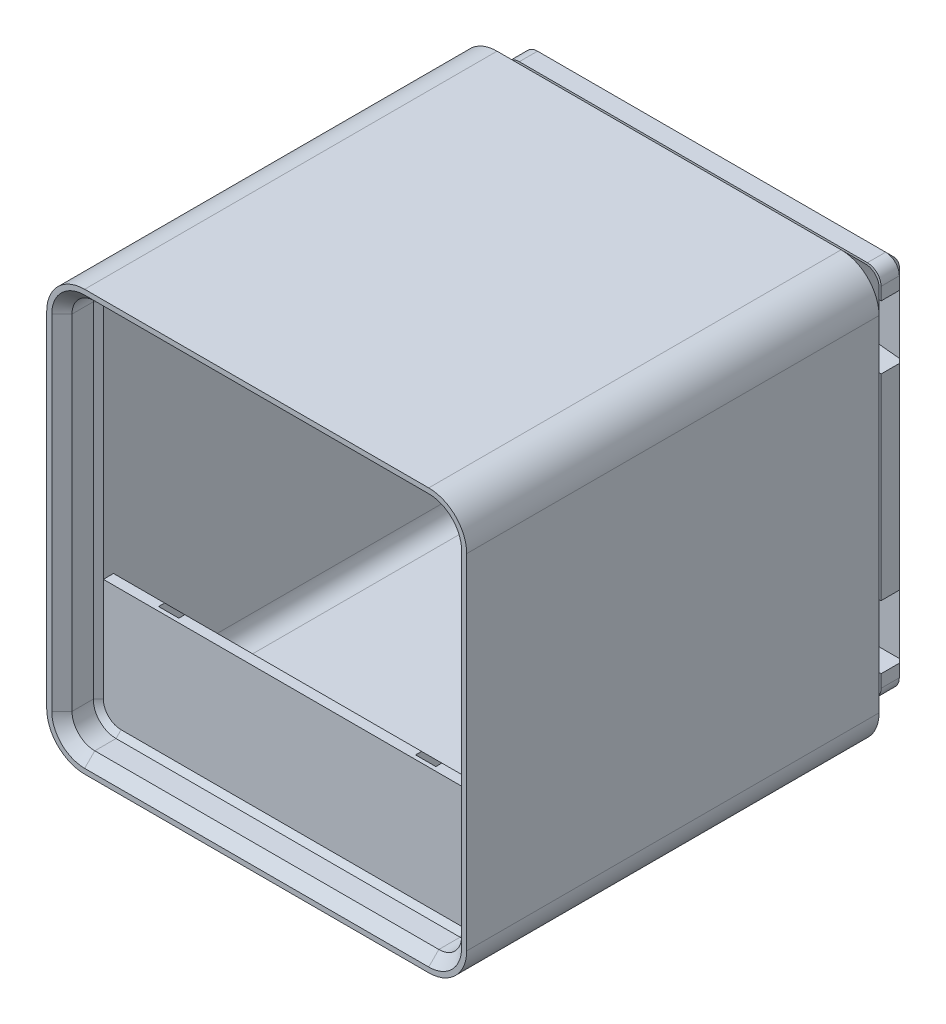
SolidWorks part; units mm, degrees
ref_plane "Front Plane" through (0, 0, 0) normal (0, 0, 1) x (1, 0, 0)
ref_plane "Top Plane" through (0, 0, 0) normal (0, 1, 0) x (1, 0, 0)
ref_plane "Right Plane" through (0, 0, 0) normal (1, 0, 0) x (0, 0, -1)
sketch "Sketch1" plane through (0, 0, 0) normal (0, 0, 1) x (1, 0, 0)
  line L1 (18.55, 18.55) -> (-18.55, 18.55)
  line L2 (18.55, 18.55) -> (18.55, -18.55)
  line L3 (18.55, -18.55) -> (-18.55, -18.55)
  line L4 (-18.55, 18.55) -> (-18.55, -18.55)
  line L5 (18.55, 18.55) -> (-18.55, -18.55) construction
  line L6 (18.55, -18.55) -> (-18.55, 18.55) construction
  point P0 (0, 0)
  dimension "D1" = 37.1
extrude "Boss-Extrude1" add sketch "Sketch1" along normal blind 2.6
sketch "Sketch2" plane through (0, 0, 2.6) normal (0, 0, 1) x (1, 0, 0)
  line L1 (-20.75, 20.75) -> (20.75, 20.75)
  line L2 (-20.75, 20.75) -> (-20.75, -20.75)
  line L3 (-20.75, -20.75) -> (20.75, -20.75)
  line L4 (20.75, 20.75) -> (20.75, -20.75)
  line L5 (-20.75, 20.75) -> (20.75, -20.75) construction
  line L6 (-20.75, -20.75) -> (20.75, 20.75) construction
  point P0 (0, 0)
  dimension "D1" = 41.5
extrude "Boss-Extrude2" add sketch "Sketch2" along normal blind 2.4
sketch "Sketch8" plane through (0, 0, 2.6) normal (0, 0, -1) x (-1, 0, 0)
  line L0 (-18.55, 18.55) -> (-18.55, 5.0094) construction
  line L1 (-18.55, -18.55) -> (-18.55, 18.55) construction
  line L2 (-14.65, 10.1) -> (-18.55, 9.7)
  line L11 (-12.7, 15.95) -> (-18.55, 15.95)
  line L12 (-12.7, 12.7) -> (-12.7, -12.7)
  line L13 (-12.7, -12.7) -> (12.7, -12.7)
  line L14 (12.7, -12.7) -> (12.7, 12.7)
  line L15 (12.7, 12.7) -> (-12.7, 12.7)
  line L16 (-12.7, 9.45) -> (-12.7, -12.7) construction
  line L22 (-18.55, 15.95) -> (-18.55, 9.7)
  arc A0 (-12.7, 15.95) -> (-12.7, 9.45) centre (-12.7, 12.7) cw
  arc A1 (-12.7, 9.45) -> (-14.65, 10.1) centre (-12.7, 12.7) cw
  dimension "D4" = 5.85
  dimension "D5" = 6.25
  dimension "D2" = 6.5
  dimension "D1" = 8.05
extrude "Base Magnet Slot" cut sketch "Sketch8" against normal blind 0.4 and the other way blind 2.2
sketch "Sketch12" plane through (0, 0, 0) normal (0, 0, -1) x (-1, 0, 0)
  line L0 (-12.7, 12.7) -> (-6.2, 12.7) construction
  line L1 (-12.7, 13.7) -> (-6.2, 13.7)
  line L2 (-12.7, 11.7) -> (-6.2, 11.7)
  arc A8 (-14.65, 10.1) -> (-12.7, 15.95) centre (-12.7, 12.7) ccw construction
  arc A9 (-14.65, 10.1) -> (-12.7, 15.95) centre (-12.7, 12.7) ccw construction
  arc A10 (-12.7, 13.7) -> (-12.7, 11.7) centre (-12.7, 12.7) ccw
  arc A11 (-6.2, 11.7) -> (-6.2, 13.7) centre (-6.2, 12.7) ccw
  point P3 (-9.45, 12.7)
  dimension "D1" = 2
  dimension "D2" = 6.5
extrude "Cut-Extrude1" cut sketch "Sketch12" against normal up to surface (2.6 mm away) up to face at (0, 0, 2.6)
mirror "Mirror1" about plane through (0, 0, 0) normal (0, 1, 0) of "Cut-Extrude1", "Base Magnet Slot"
mirror "Mirror2" about plane through (0, 0, 0) normal (1, 0, 0) of "Mirror1"
fillet "Fillet1" radius 1.35 4 edges at (18.55, 18.55, 1.3) (18.55, -18.55, 1.3) (-18.55, -18.55, 1.3) (-18.55, 18.55, 1.3)
fillet "Fillet2" radius 3.75 4 edges at (20.75, -20.75, 3.8) (20.75, 20.75, 3.8) (-20.75, -20.75, 3.8) (-20.75, 20.75, 3.8)
chamfer "Chamfer1" distance 0.8 angle 45 8 edges at (-18.1546, 18.1546, 0) (-18.55, 0, 0) (-18.1546, -18.1546, 0) (0, -18.55, 0) (18.1546, -18.1546, 0) (18.55, 0, 0) (18.1546, 18.1546, 0) (0, 18.55, 0)
chamfer "Chamfer2" distance 2.4 angle 45 8 edges at (20.75, 0, 2.6) (19.6517, 19.6517, 2.6) (19.6517, -19.6517, 2.6) (0, 20.75, 2.6) (0, -20.75, 2.6) (-19.6517, 19.6517, 2.6) (-19.6517, -19.6517, 2.6) (-20.75, 0, 2.6)
sketch "Sketch5" plane through (0, 0, 5) normal (0, 0, 1) x (1, 0, 0)
  line L32 (-17, -18.75) -> (17, -18.75)
  line L33 (18.75, -17) -> (18.75, 17)
  line L42 (17, 18.75) -> (-17, 18.75)
  line L56 (-18.75, 17) -> (-18.75, -17)
  line L57 (-17, -20.75) -> (17, -20.75)
  line L58 (20.75, -17) -> (20.75, 17)
  line L59 (17, 20.75) -> (-17, 20.75)
  line L60 (-20.75, 17) -> (-20.75, -17)
  line L61 (-17, -20.75) -> (17, -20.75)
  line L62 (20.75, -17) -> (20.75, 17)
  line L63 (17, 20.75) -> (-17, 20.75)
  line L64 (-20.75, 17) -> (-20.75, -17)
  arc A24 (17, -18.75) -> (18.75, -17) centre (17, -17) ccw
  arc A25 (18.75, 17) -> (17, 18.75) centre (17, 17) ccw
  arc A26 (-17, 18.75) -> (-18.75, 17) centre (-17, 17) ccw
  arc A27 (-18.75, -17) -> (-17, -18.75) centre (-17, -17) ccw
  arc A30 (17, -20.75) -> (20.75, -17) centre (17, -17) ccw
  arc A31 (20.75, 17) -> (17, 20.75) centre (17, 17) ccw
  arc A32 (-17, 20.75) -> (-20.75, 17) centre (-17, 17) ccw
  arc A33 (-20.75, -17) -> (-17, -20.75) centre (-17, -17) ccw
  arc A34 (17, -20.75) -> (20.75, -17) centre (17, -17) ccw
  arc A35 (20.75, 17) -> (17, 20.75) centre (17, 17) ccw
  arc A36 (-17, 20.75) -> (-20.75, 17) centre (-17, 17) ccw
  arc A37 (-20.75, -17) -> (-17, -20.75) centre (-17, -17) ccw
  dimension "D1" = 0
  dimension "D2" = 2
extrude "Side Walls" add sketch "Sketch5" along normal blind 36.85
sketch "Sketch11" plane through (0, 0, 41.85) normal (0, 0, 1) x (1, 0, 0)
  line L24 (-17, -20.75) -> (17, -20.75) construction
  line L25 (20.75, -17) -> (20.75, 17) construction
  line L26 (17, 20.75) -> (-17, 20.75) construction
  line L27 (-20.75, 17) -> (-20.75, -17) construction
  line L28 (-17, -20.75) -> (17, -20.75)
  line L29 (20.75, -17) -> (20.75, 17)
  line L30 (17, 20.75) -> (-17, 20.75)
  line L31 (-20.75, 17) -> (-20.75, -17)
  line L32 (-17, -19.25) -> (17, -19.25)
  line L33 (19.25, -17) -> (19.25, 17)
  line L34 (17, 19.25) -> (-17, 19.25)
  line L35 (-19.25, 17) -> (-19.25, -17)
  arc A24 (-20.75, -17) -> (-17, -20.75) centre (-17, -17) ccw construction
  arc A25 (17, -20.75) -> (20.75, -17) centre (17, -17) ccw construction
  arc A26 (20.75, 17) -> (17, 20.75) centre (17, 17) ccw construction
  arc A27 (-17, 20.75) -> (-20.75, 17) centre (-17, 17) ccw construction
  arc A28 (-20.75, -17) -> (-17, -20.75) centre (-17, -17) ccw
  arc A29 (17, -20.75) -> (20.75, -17) centre (17, -17) ccw
  arc A30 (20.75, 17) -> (17, 20.75) centre (17, 17) ccw
  arc A31 (-17, 20.75) -> (-20.75, 17) centre (-17, 17) ccw
  arc A32 (17, -19.25) -> (19.25, -17) centre (17, -17) ccw
  arc A33 (19.25, 17) -> (17, 19.25) centre (17, 17) ccw
  arc A34 (-17, 19.25) -> (-19.25, 17) centre (-17, 17) ccw
  arc A35 (-19.25, -17) -> (-17, -19.25) centre (-17, -17) ccw
extrude "Boss-Extrude4" add sketch "Sketch11" along normal blind 3.9
chamfer "Chamfer3" distance 0.8 angle 45 8 edges at (0, -19.25, 41.85) (18.591, -18.591, 41.85) (-18.591, -18.591, 41.85) (19.25, 0, 41.85) (-19.25, 0, 41.85) (18.591, 18.591, 41.85) (-18.591, 18.591, 41.85) (0, 19.25, 41.85)
chamfer "Chamfer4" distance 1 angle 45 8 edges at (0, -19.25, 45.75) (18.591, -18.591, 45.75) (-18.591, -18.591, 45.75) (19.25, 0, 45.75) (-19.25, 0, 45.75) (18.591, 18.591, 45.75) (-18.591, 18.591, 45.75) (0, 19.25, 45.75)
sketch "Sketch13" plane through (18.75, 0, 0) normal (-1, 0, 0) x (0, 0, 1)
  line L0 (5, -17) -> (5, 17) construction
  line L1 (42.15, 18.75) -> (5, 18.75) construction
  line L2 (5, -1.25) -> (5, 18.75)
  line L3 (25, 18.75) -> (5, 18.75)
  arc A0 (25, 18.75) -> (5, -1.25) centre (25, -1.25) ccw
  dimension "D1" = 20
extrude "Internal Ramp" add sketch "Sketch13" along normal up to surface (37.5 mm away) up to face at (-18.75, 0, 23.575)
ref_plane "Plane1" through (0, 0, 42.15) normal (0, 0, -1) x (-1, 0, 0)
sketch "Sketch14" plane through (0, 0, 42.15) normal (0, 0, -1) x (-1, 0, 0)
  line L0 (-18.75, -17) -> (-18.75, 17) construction
  line L1 (17, -18.75) -> (-17, -18.75) construction
  line L2 (18.75, 17) -> (18.75, -17) construction
  line L3 (-18.75, -17) -> (-18.75, -6.75)
  line L4 (17, -18.75) -> (-17, -18.75)
  line L5 (18.75, -6.75) -> (18.75, -17)
  line L6 (-18.75, -6.75) -> (18.75, -6.75)
  arc A0 (-18.75, -17) -> (-17, -18.75) centre (-17, -17) ccw construction
  arc A1 (17, -18.75) -> (18.75, -17) centre (17, -17) ccw construction
  arc A2 (-18.75, -17) -> (-17, -18.75) centre (-17, -17) ccw
  arc A3 (17, -18.75) -> (18.75, -17) centre (17, -17) ccw
  dimension "D1" = 12
extrude "Boss-Extrude6" add sketch "Sketch14" along normal blind 12
chamfer "Chamfer5" distance 11 angle 45 1 edges at (0, -6.75, 30.15)
ref_plane "Offset Plane" through (0, 0, 41.75) normal (0, 0, 1) x (1, 0, 0)
sketch "Sketch17" plane through (0, 0, 41.75) normal (0, 0, 1) x (1, 0, 0)
  line L0 (-17, -20.75) -> (17, -20.75) construction
  line L1 (-17, -20.75) -> (17, -20.75) construction
  line L2 (-20.75, -12.7) -> (20.75, -12.7) construction
  line L3 (-20.75, 17) -> (-20.75, -17) construction
  line L4 (20.75, -17) -> (20.75, 17) construction
  line L5 (-20.75, 17) -> (-20.75, -17) construction
  line L6 (-12.7, -11.0494) -> (-12.7, 18.75) construction
  line L7 (-17, 18.75) -> (17, 18.75) construction
  line L8 (-15.95, -12.7) -> (-15.95, -20.75)
  line L9 (-15.95, -20.75) -> (-9.45, -20.75)
  line L10 (-10.1, -14.65) -> (-9.45, -20.75)
  line L11 (-12.7, -12.7) -> (-12.7, -4.7) construction
  line L13 (-13.7, -9.6077) -> (-13.7, -4.7)
  line L14 (-11.7, -9.6077) -> (-11.7, -4.7)
  arc A0 (-15.95, -12.7) -> (-13.7, -9.6077) centre (-12.7, -12.7) cw
  arc A2 (-11.7, -4.7) -> (-13.7, -4.7) centre (-12.7, -4.7) ccw
  arc A3 (-11.7, -9.6077) -> (-10.1, -14.65) centre (-12.7, -12.7) cw
  point P20 (-12.7, -8.7)
  dimension "D3" = 3.25
  dimension "D1" = 8.05
  dimension "D2" = 8.05
  dimension "D4" = 6.5
  dimension "D5" = 5.85
extrude "Cut-Extrude2" cut sketch "Sketch17" against normal blind 2.6
mirror "Mirror3" about plane through (0, 0, 0) normal (1, 0, 0) of "Cut-Extrude2"
equation "\"MagnetHoleDia\"= 6.5"
equation "\"MagnetPressGap\"= 5.85"
equation "\"MagnetSlotDepth\"= 2.6"
equation "\"D2@Sketch17\"=\"D1@Sketch17\""
equation "\"D3@Sketch17\"=\"MagnetHoleDia\"/2"
